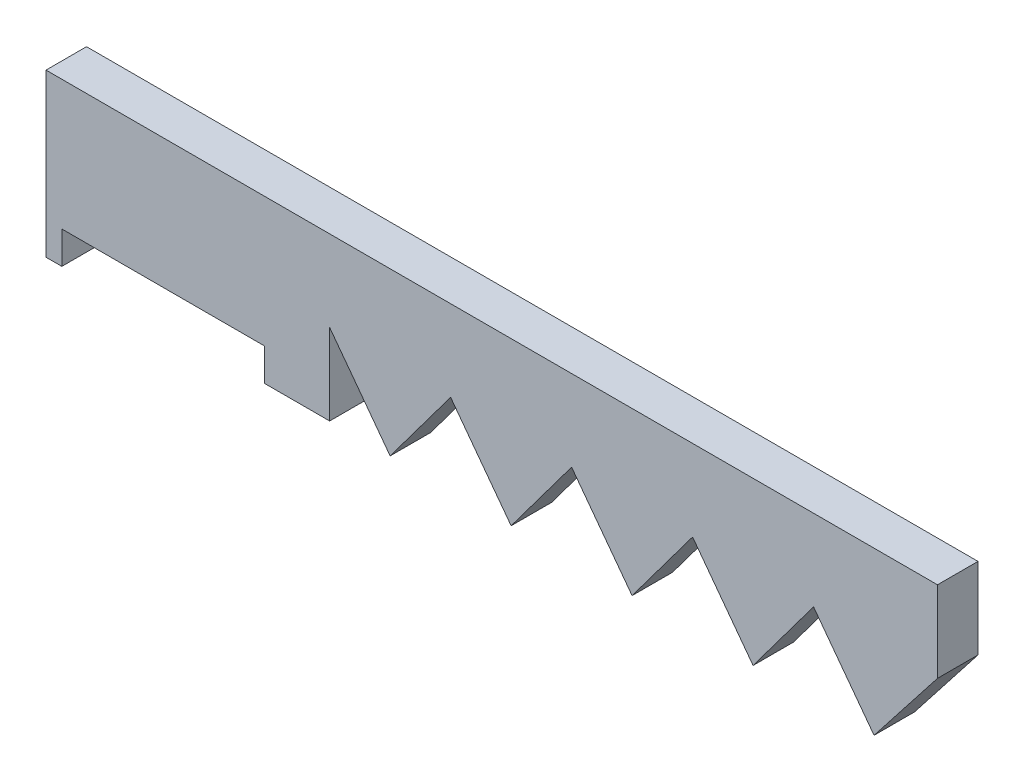
SolidWorks part; units mm, degrees
ref_plane "Front Plane" through (0, 0, 0) normal (0, 0, 1) x (1, 0, 0)
ref_plane "Top Plane" through (0, 0, 0) normal (0, 1, 0) x (1, 0, 0)
ref_plane "Right Plane" through (0, 0, 0) normal (1, 0, 0) x (0, 0, -1)
sketch "Sketch1" plane through (0, 0, 0) normal (0, 0, 1) x (1, 0, 0)
  line L0 (55, 0) -> (-55, 0) construction
  line L1 (-27.94, 0) -> (-10.16, 0)
  line L2 (-27.94, 0) -> (-27.94, 10.16)
  line L3 (-27.94, 10.16) -> (27.94, 10.16)
  line L4 (27.94, 5.08) -> (27.94, 10.16)
  line L5 (-10.16, 5.08) -> (-10.16, 0)
  line L6 (-10.16, 5.08) -> (-6.3684, 0)
  line L7 (-6.3684, 0) -> (-2.5768, 5.08)
  line L8 (-2.5768, 5.08) -> (1.2148, 0)
  line L9 (1.2148, 0) -> (5.0064, 5.08)
  line L10 (5.0064, 5.08) -> (8.798, 0)
  line L11 (8.798, 0) -> (12.5896, 5.08)
  line L12 (27.94, 5.08) -> (-10.16, 5.08) construction
  line L13 (12.5896, 5.08) -> (16.3812, 0)
  line L14 (16.3812, 0) -> (20.1728, 5.08)
  line L15 (20.1728, 5.08) -> (23.9644, 0)
  line L16 (23.9644, 0) -> (27.94, 5.08)
  point P6 (0, 10.16)
  dimension "D1" = 10.16
  dimension "D2" = 5.08
  dimension "D3" = 53.263
  dimension "D4" = 51.953
  dimension "D5" = 17.78
extrude "Boss-Extrude1" add sketch "Sketch1" along normal blind 2.54
sketch "Sketch2" plane through (0, 0, 0) normal (0, -1, 0) x (1, 0, 0)
  line L1 (-26.947, 0) -> (-14.247, 0)
  line L2 (-26.947, 0) -> (-26.947, 2.54)
  line L3 (-26.947, 2.54) -> (-14.247, 2.54)
  line L6 (-27.94, 2.54) -> (-27.94, 0) construction
  arc A0 (-14.247, 2.54) -> (-14.247, 0) centre (-15.3597, 1.27) cw
  dimension "D1" = 1.6885
  dimension "D2" = 1.1127
  dimension "D3" = 0.993
  dimension "D4" = 2.54
  dimension "D5" = 12.7
extrude "Cut-Extrude2" cut sketch "Sketch2" against normal blind 2.032
